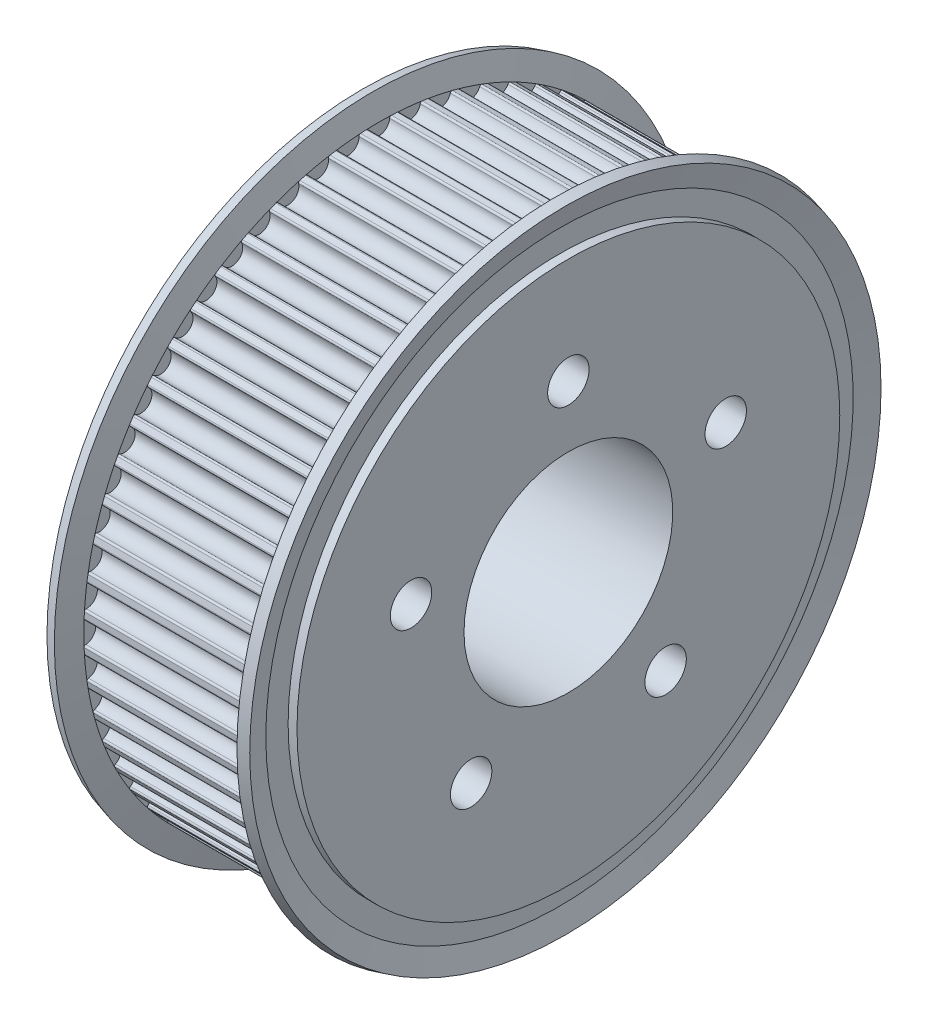
SolidWorks part; units mm, degrees
ref_plane "Front Plane" through (0, 0, 0) normal (0, 0, 1) x (1, 0, 0)
ref_plane "Top Plane" through (0, 0, 0) normal (0, 1, 0) x (1, 0, 0)
ref_plane "Right Plane" through (0, 0, 0) normal (1, 0, 0) x (0, 0, -1)
ref_plane "Plane1" through (0, 0, 0) normal (0, 0, 1) x (1, 0, 0)
sketch "Sketch1" plane through (0, 0, 0) normal (0, 0, 1) x (1, 0, 0)
  line L0 (0, 0) -> (0, 26)
  line L1 (0, 26) -> (0.85, 26)
  line L2 (0.85, 26) -> (0.85, 28.1383)
  line L3 (0.85, 28.1383) -> (0.2865, 30.2412)
  line L4 (0.2865, 30.2412) -> (1.2525, 30.5)
  line L5 (1.2525, 30.5) -> (1.85, 28.27)
  line L6 (1.85, 28.27) -> (18.15, 28.27)
  line L7 (18.15, 28.27) -> (18.7475, 30.5)
  line L8 (18.7475, 30.5) -> (19.7135, 30.2412)
  line L9 (19.7135, 30.2412) -> (19.15, 28.1383)
  line L10 (19.15, 28.1383) -> (19.15, 26)
  line L11 (19.15, 26) -> (20, 26)
  line L12 (20, 26) -> (20, 0)
  line L13 (20, 0) -> (0, 0)
  line L14 (20, 0) -> (0, 0) construction
revolve "Revolve1" add sketch "Sketch1" angle 360 about L14 reverse direction yes
ref_plane "Plane2" through (10, 0, 0) normal (1, 0, 0) x (0, 0, -1)
sketch "Sketch2" plane through (10, 0, 0) normal (1, 0, 0) x (0, 0, -1)
  line L0 (-1.2204, 28.624) -> (-1.2042, 28.2443)
  line L1 (1.2042, 28.2443) -> (1.2204, 28.624)
  arc A0 (-1.2042, 28.2443) -> (-1.0274, 28.0866) centre (-1.1969, 28.0745) cw
  arc A1 (-1.0274, 28.0866) -> (1.0274, 28.0866) centre (0, 28.16) ccw
  arc A2 (1.0274, 28.0866) -> (1.2042, 28.2443) centre (1.1969, 28.0745) cw
  arc A3 (1.2204, 28.624) -> (-1.2204, 28.624) centre (0, 0) ccw
extrude "Cut-Extrude1" cut sketch "Sketch2" against normal blind 8.15 and the other way blind 8.15
ref_plane "Plane3" through (10, 0, 0) normal (1, 0, 0) x (0, 0, -1)
sketch "Sketch3" plane through (10, 0, 0) normal (1, 0, 0) x (0, 0, -1)
  line L0 (-4.2057, 28.3396) -> (-4.1499, 27.9637)
  line L1 (-1.7547, 28.2155) -> (-1.7783, 28.5948)
  arc A0 (-4.1499, 27.9637) -> (-3.9576, 27.8254) centre (-4.125, 27.7956) cw
  arc A1 (-3.9576, 27.8254) -> (-1.9141, 28.0401) centre (-2.9435, 28.0057) ccw
  arc A2 (-1.9141, 28.0401) -> (-1.7547, 28.2155) centre (-1.7442, 28.0458) cw
  arc A3 (-1.7783, 28.5948) -> (-4.2057, 28.3396) centre (0, 0) ccw
extrude "Cut-Extrude2" cut sketch "Sketch3" against normal blind 8.15 and the other way blind 8.15
ref_plane "Plane4" through (10, 0, 0) normal (1, 0, 0) x (0, 0, -1)
sketch "Sketch4" plane through (10, 0, 0) normal (1, 0, 0) x (0, 0, -1)
  line L0 (-7.145, 27.7448) -> (-7.0502, 27.3768)
  line L1 (-4.6945, 27.8775) -> (-4.7576, 28.2522)
  arc A0 (-7.0502, 27.3768) -> (-6.8445, 27.2592) centre (-7.0078, 27.2121) cw
  arc A1 (-6.8445, 27.2592) -> (-4.8346, 27.6865) centre (-5.8548, 27.5446) ccw
  arc A2 (-4.8346, 27.6865) -> (-4.6945, 27.8775) centre (-4.6662, 27.7099) cw
  arc A3 (-4.7576, 28.2522) -> (-7.145, 27.7448) centre (0, 0) ccw
extrude "Cut-Extrude3" cut sketch "Sketch4" against normal blind 8.15 and the other way blind 8.15
ref_plane "Plane5" through (10, 0, 0) normal (1, 0, 0) x (0, 0, -1)
sketch "Sketch5" plane through (10, 0, 0) normal (1, 0, 0) x (0, 0, -1)
  line L0 (-10.0059, 26.8459) -> (-9.8732, 26.4898)
  line L1 (-7.5827, 27.2341) -> (-7.6847, 27.6002)
  arc A0 (-9.8732, 26.4898) -> (-9.6563, 26.3945) centre (-9.8139, 26.3306) cw
  arc A1 (-9.6563, 26.3945) -> (-7.7021, 27.0294) centre (-8.7019, 26.7818) ccw
  arc A2 (-7.7021, 27.0294) -> (-7.5827, 27.2341) centre (-7.5371, 27.0703) cw
  arc A3 (-7.6847, 27.6002) -> (-10.0059, 26.8459) centre (0, 0) ccw
extrude "Cut-Extrude4" cut sketch "Sketch5" against normal blind 8.15 and the other way blind 8.15
ref_plane "Plane6" through (10, 0, 0) normal (1, 0, 0) x (0, 0, -1)
sketch "Sketch6" plane through (10, 0, 0) normal (1, 0, 0) x (0, 0, -1)
  line L0 (-12.7573, 25.6529) -> (-12.5881, 25.3127)
  line L1 (-10.3879, 26.2923) -> (-10.5276, 26.6457)
  arc A0 (-12.5881, 25.3127) -> (-12.3624, 25.2405) centre (-12.5124, 25.1605) cw
  arc A1 (-12.3624, 25.2405) -> (-10.4853, 26.0763) centre (-11.4537, 25.7254) ccw
  arc A2 (-10.4853, 26.0763) -> (-10.3879, 26.2923) centre (-10.3255, 26.1342) cw
  arc A3 (-10.5276, 26.6457) -> (-12.7573, 25.6529) centre (0, 0) ccw
extrude "Cut-Extrude5" cut sketch "Sketch6" against normal blind 8.15 and the other way blind 8.15
ref_plane "Plane7" through (10, 0, 0) normal (1, 0, 0) x (0, 0, -1)
sketch "Sketch7" plane through (10, 0, 0) normal (1, 0, 0) x (0, 0, -1)
  line L0 (-15.3689, 24.1789) -> (-15.165, 23.8582)
  line L1 (-13.0793, 25.0624) -> (-13.2551, 25.3993)
  arc A0 (-15.165, 23.8582) -> (-14.933, 23.81) centre (-15.0738, 23.7148) cw
  arc A1 (-14.933, 23.81) -> (-13.1536, 24.8374) centre (-14.08, 24.3873) ccw
  arc A2 (-13.1536, 24.8374) -> (-13.0793, 25.0624) centre (-13.0007, 24.9117) cw
  arc A3 (-13.2551, 25.3993) -> (-15.3689, 24.1789) centre (0, 0) ccw
extrude "Cut-Extrude6" cut sketch "Sketch7" against normal blind 8.15 and the other way blind 8.15
ref_plane "Plane8" through (10, 0, 0) normal (1, 0, 0) x (0, 0, -1)
sketch "Sketch8" plane through (10, 0, 0) normal (1, 0, 0) x (0, 0, -1)
  line L0 (-17.8121, 22.44) -> (-17.5758, 22.1423)
  line L1 (-15.6274, 23.558) -> (-15.8375, 23.8746)
  arc A0 (-17.5758, 22.1423) -> (-17.3401, 22.1187) centre (-17.4701, 22.0092) cw
  arc A1 (-17.3401, 22.1187) -> (-15.6777, 23.3264) centre (-16.552, 22.7819) ccw
  arc A2 (-15.6777, 23.3264) -> (-15.6274, 23.558) centre (-15.5334, 23.4163) cw
  arc A3 (-15.8375, 23.8746) -> (-17.8121, 22.44) centre (0, 0) ccw
extrude "Cut-Extrude7" cut sketch "Sketch8" against normal blind 8.15 and the other way blind 8.15
ref_plane "Plane9" through (10, 0, 0) normal (1, 0, 0) x (0, 0, -1)
sketch "Sketch9" plane through (10, 0, 0) normal (1, 0, 0) x (0, 0, -1)
  line L0 (-20.0601, 20.4552) -> (-19.794, 20.1839)
  line L1 (-18.0043, 21.7954) -> (-18.2463, 22.0884)
  arc A0 (-19.794, 20.1839) -> (-19.5571, 20.185) centre (-19.675, 20.0625) cw
  arc A1 (-19.5571, 20.185) -> (-18.0301, 21.5599) centre (-18.8427, 20.927) ccw
  arc A2 (-18.0301, 21.5599) -> (-18.0043, 21.7954) centre (-17.896, 21.6643) cw
  arc A3 (-18.2463, 22.0884) -> (-20.0601, 20.4552) centre (0, 0) ccw
extrude "Cut-Extrude8" cut sketch "Sketch9" against normal blind 8.15 and the other way blind 8.15
ref_plane "Plane10" through (10, 0, 0) normal (1, 0, 0) x (0, 0, -1)
sketch "Sketch10" plane through (10, 0, 0) normal (1, 0, 0) x (0, 0, -1)
  line L0 (-22.0884, 18.2463) -> (-21.7954, 18.0043)
  line L1 (-20.1839, 19.794) -> (-20.4552, 20.0601)
  arc A0 (-21.7954, 18.0043) -> (-21.5599, 18.0301) centre (-21.6643, 17.896) cw
  arc A1 (-21.5599, 18.0301) -> (-20.185, 19.5571) centre (-20.927, 18.8427) ccw
  arc A2 (-20.185, 19.5571) -> (-20.1839, 19.794) centre (-20.0625, 19.675) cw
  arc A3 (-20.4552, 20.0601) -> (-22.0884, 18.2463) centre (0, 0) ccw
extrude "Cut-Extrude9" cut sketch "Sketch10" against normal blind 8.15 and the other way blind 8.15
ref_plane "Plane11" through (10, 0, 0) normal (1, 0, 0) x (0, 0, -1)
sketch "Sketch11" plane through (10, 0, 0) normal (1, 0, 0) x (0, 0, -1)
  line L0 (-23.8746, 15.8375) -> (-23.558, 15.6274)
  line L1 (-22.1423, 17.5758) -> (-22.44, 17.8121)
  arc A0 (-23.558, 15.6274) -> (-23.3264, 15.6777) centre (-23.4163, 15.5334) cw
  arc A1 (-23.3264, 15.6777) -> (-22.1187, 17.3401) centre (-22.7819, 16.552) ccw
  arc A2 (-22.1187, 17.3401) -> (-22.1423, 17.5758) centre (-22.0092, 17.4701) cw
  arc A3 (-22.44, 17.8121) -> (-23.8746, 15.8375) centre (0, 0) ccw
extrude "Cut-Extrude10" cut sketch "Sketch11" against normal blind 8.15 and the other way blind 8.15
ref_plane "Plane12" through (10, 0, 0) normal (1, 0, 0) x (0, 0, -1)
sketch "Sketch12" plane through (10, 0, 0) normal (1, 0, 0) x (0, 0, -1)
  line L0 (-25.3993, 13.2551) -> (-25.0624, 13.0793)
  line L1 (-23.8582, 15.165) -> (-24.1789, 15.3689)
  arc A0 (-25.0624, 13.0793) -> (-24.8374, 13.1536) centre (-24.9117, 13.0007) cw
  arc A1 (-24.8374, 13.1536) -> (-23.81, 14.933) centre (-24.3873, 14.08) ccw
  arc A2 (-23.81, 14.933) -> (-23.8582, 15.165) centre (-23.7148, 15.0738) cw
  arc A3 (-24.1789, 15.3689) -> (-25.3993, 13.2551) centre (0, 0) ccw
extrude "Cut-Extrude11" cut sketch "Sketch12" against normal blind 8.15 and the other way blind 8.15
ref_plane "Plane13" through (10, 0, 0) normal (1, 0, 0) x (0, 0, -1)
sketch "Sketch13" plane through (10, 0, 0) normal (1, 0, 0) x (0, 0, -1)
  line L0 (-26.6457, 10.5276) -> (-26.2923, 10.3879)
  line L1 (-25.3127, 12.5881) -> (-25.6529, 12.7573)
  arc A0 (-26.2923, 10.3879) -> (-26.0763, 10.4853) centre (-26.1342, 10.3255) cw
  arc A1 (-26.0763, 10.4853) -> (-25.2405, 12.3624) centre (-25.7254, 11.4537) ccw
  arc A2 (-25.2405, 12.3624) -> (-25.3127, 12.5881) centre (-25.1605, 12.5124) cw
  arc A3 (-25.6529, 12.7573) -> (-26.6457, 10.5276) centre (0, 0) ccw
extrude "Cut-Extrude12" cut sketch "Sketch13" against normal blind 8.15 and the other way blind 8.15
ref_plane "Plane14" through (10, 0, 0) normal (1, 0, 0) x (0, 0, -1)
sketch "Sketch14" plane through (10, 0, 0) normal (1, 0, 0) x (0, 0, -1)
  line L0 (-27.6002, 7.6847) -> (-27.2341, 7.5827)
  line L1 (-26.4898, 9.8732) -> (-26.8459, 10.0059)
  arc A0 (-27.2341, 7.5827) -> (-27.0294, 7.7021) centre (-27.0703, 7.5371) cw
  arc A1 (-27.0294, 7.7021) -> (-26.3945, 9.6563) centre (-26.7818, 8.7019) ccw
  arc A2 (-26.3945, 9.6563) -> (-26.4898, 9.8732) centre (-26.3306, 9.8139) cw
  arc A3 (-26.8459, 10.0059) -> (-27.6002, 7.6847) centre (0, 0) ccw
extrude "Cut-Extrude13" cut sketch "Sketch14" against normal blind 8.15 and the other way blind 8.15
ref_plane "Plane15" through (10, 0, 0) normal (1, 0, 0) x (0, 0, -1)
sketch "Sketch15" plane through (10, 0, 0) normal (1, 0, 0) x (0, 0, -1)
  line L0 (-28.2522, 4.7576) -> (-27.8775, 4.6945)
  line L1 (-27.3768, 7.0502) -> (-27.7448, 7.145)
  arc A0 (-27.8775, 4.6945) -> (-27.6865, 4.8346) centre (-27.7099, 4.6662) cw
  arc A1 (-27.6865, 4.8346) -> (-27.2592, 6.8445) centre (-27.5446, 5.8548) ccw
  arc A2 (-27.2592, 6.8445) -> (-27.3768, 7.0502) centre (-27.2121, 7.0078) cw
  arc A3 (-27.7448, 7.145) -> (-28.2522, 4.7576) centre (0, 0) ccw
extrude "Cut-Extrude14" cut sketch "Sketch15" against normal blind 8.15 and the other way blind 8.15
ref_plane "Plane16" through (10, 0, 0) normal (1, 0, 0) x (0, 0, -1)
sketch "Sketch16" plane through (10, 0, 0) normal (1, 0, 0) x (0, 0, -1)
  line L0 (-28.5948, 1.7783) -> (-28.2155, 1.7547)
  line L1 (-27.9637, 4.1499) -> (-28.3396, 4.2057)
  arc A0 (-28.2155, 1.7547) -> (-28.0401, 1.9141) centre (-28.0458, 1.7442) cw
  arc A1 (-28.0401, 1.9141) -> (-27.8254, 3.9576) centre (-28.0057, 2.9435) ccw
  arc A2 (-27.8254, 3.9576) -> (-27.9637, 4.1499) centre (-27.7956, 4.125) cw
  arc A3 (-28.3396, 4.2057) -> (-28.5948, 1.7783) centre (0, 0) ccw
extrude "Cut-Extrude15" cut sketch "Sketch16" against normal blind 8.15 and the other way blind 8.15
ref_plane "Plane17" through (10, 0, 0) normal (1, 0, 0) x (0, 0, -1)
sketch "Sketch17" plane through (10, 0, 0) normal (1, 0, 0) x (0, 0, -1)
  line L0 (-28.624, -1.2204) -> (-28.2443, -1.2042)
  line L1 (-28.2443, 1.2042) -> (-28.624, 1.2204)
  arc A0 (-28.2443, -1.2042) -> (-28.0866, -1.0274) centre (-28.0745, -1.1969) cw
  arc A1 (-28.0866, -1.0274) -> (-28.0866, 1.0274) centre (-28.16, 0) ccw
  arc A2 (-28.0866, 1.0274) -> (-28.2443, 1.2042) centre (-28.0745, 1.1969) cw
  arc A3 (-28.624, 1.2204) -> (-28.624, -1.2204) centre (0, 0) ccw
extrude "Cut-Extrude16" cut sketch "Sketch17" against normal blind 8.15 and the other way blind 8.15
ref_plane "Plane18" through (10, 0, 0) normal (1, 0, 0) x (0, 0, -1)
sketch "Sketch18" plane through (10, 0, 0) normal (1, 0, 0) x (0, 0, -1)
  line L0 (-28.3396, -4.2057) -> (-27.9637, -4.1499)
  line L1 (-28.2155, -1.7547) -> (-28.5948, -1.7783)
  arc A0 (-27.9637, -4.1499) -> (-27.8254, -3.9576) centre (-27.7956, -4.125) cw
  arc A1 (-27.8254, -3.9576) -> (-28.0401, -1.9141) centre (-28.0057, -2.9435) ccw
  arc A2 (-28.0401, -1.9141) -> (-28.2155, -1.7547) centre (-28.0458, -1.7442) cw
  arc A3 (-28.5948, -1.7783) -> (-28.3396, -4.2057) centre (0, 0) ccw
extrude "Cut-Extrude17" cut sketch "Sketch18" against normal blind 8.15 and the other way blind 8.15
ref_plane "Plane19" through (10, 0, 0) normal (1, 0, 0) x (0, 0, -1)
sketch "Sketch19" plane through (10, 0, 0) normal (1, 0, 0) x (0, 0, -1)
  line L0 (-27.7448, -7.145) -> (-27.3768, -7.0502)
  line L1 (-27.8775, -4.6945) -> (-28.2522, -4.7576)
  arc A0 (-27.3768, -7.0502) -> (-27.2592, -6.8445) centre (-27.2121, -7.0078) cw
  arc A1 (-27.2592, -6.8445) -> (-27.6865, -4.8346) centre (-27.5446, -5.8548) ccw
  arc A2 (-27.6865, -4.8346) -> (-27.8775, -4.6945) centre (-27.7099, -4.6662) cw
  arc A3 (-28.2522, -4.7576) -> (-27.7448, -7.145) centre (0, 0) ccw
extrude "Cut-Extrude18" cut sketch "Sketch19" against normal blind 8.15 and the other way blind 8.15
ref_plane "Plane20" through (10, 0, 0) normal (1, 0, 0) x (0, 0, -1)
sketch "Sketch20" plane through (10, 0, 0) normal (1, 0, 0) x (0, 0, -1)
  line L0 (-26.8459, -10.0059) -> (-26.4898, -9.8732)
  line L1 (-27.2341, -7.5827) -> (-27.6002, -7.6847)
  arc A0 (-26.4898, -9.8732) -> (-26.3945, -9.6563) centre (-26.3306, -9.8139) cw
  arc A1 (-26.3945, -9.6563) -> (-27.0294, -7.7021) centre (-26.7818, -8.7019) ccw
  arc A2 (-27.0294, -7.7021) -> (-27.2341, -7.5827) centre (-27.0703, -7.5371) cw
  arc A3 (-27.6002, -7.6847) -> (-26.8459, -10.0059) centre (0, 0) ccw
extrude "Cut-Extrude19" cut sketch "Sketch20" against normal blind 8.15 and the other way blind 8.15
ref_plane "Plane21" through (10, 0, 0) normal (1, 0, 0) x (0, 0, -1)
sketch "Sketch21" plane through (10, 0, 0) normal (1, 0, 0) x (0, 0, -1)
  line L0 (-25.6529, -12.7573) -> (-25.3127, -12.5881)
  line L1 (-26.2923, -10.3879) -> (-26.6457, -10.5276)
  arc A0 (-25.3127, -12.5881) -> (-25.2405, -12.3624) centre (-25.1605, -12.5124) cw
  arc A1 (-25.2405, -12.3624) -> (-26.0763, -10.4853) centre (-25.7254, -11.4537) ccw
  arc A2 (-26.0763, -10.4853) -> (-26.2923, -10.3879) centre (-26.1342, -10.3255) cw
  arc A3 (-26.6457, -10.5276) -> (-25.6529, -12.7573) centre (0, 0) ccw
extrude "Cut-Extrude20" cut sketch "Sketch21" against normal blind 8.15 and the other way blind 8.15
ref_plane "Plane22" through (10, 0, 0) normal (1, 0, 0) x (0, 0, -1)
sketch "Sketch22" plane through (10, 0, 0) normal (1, 0, 0) x (0, 0, -1)
  line L0 (-24.1789, -15.3689) -> (-23.8582, -15.165)
  line L1 (-25.0624, -13.0793) -> (-25.3993, -13.2551)
  arc A0 (-23.8582, -15.165) -> (-23.81, -14.933) centre (-23.7148, -15.0738) cw
  arc A1 (-23.81, -14.933) -> (-24.8374, -13.1536) centre (-24.3873, -14.08) ccw
  arc A2 (-24.8374, -13.1536) -> (-25.0624, -13.0793) centre (-24.9117, -13.0007) cw
  arc A3 (-25.3993, -13.2551) -> (-24.1789, -15.3689) centre (0, 0) ccw
extrude "Cut-Extrude21" cut sketch "Sketch22" against normal blind 8.15 and the other way blind 8.15
ref_plane "Plane23" through (10, 0, 0) normal (1, 0, 0) x (0, 0, -1)
sketch "Sketch23" plane through (10, 0, 0) normal (1, 0, 0) x (0, 0, -1)
  line L0 (-22.44, -17.8121) -> (-22.1423, -17.5758)
  line L1 (-23.558, -15.6274) -> (-23.8746, -15.8375)
  arc A0 (-22.1423, -17.5758) -> (-22.1187, -17.3401) centre (-22.0092, -17.4701) cw
  arc A1 (-22.1187, -17.3401) -> (-23.3264, -15.6777) centre (-22.7819, -16.552) ccw
  arc A2 (-23.3264, -15.6777) -> (-23.558, -15.6274) centre (-23.4163, -15.5334) cw
  arc A3 (-23.8746, -15.8375) -> (-22.44, -17.8121) centre (0, 0) ccw
extrude "Cut-Extrude22" cut sketch "Sketch23" against normal blind 8.15 and the other way blind 8.15
ref_plane "Plane24" through (10, 0, 0) normal (1, 0, 0) x (0, 0, -1)
sketch "Sketch24" plane through (10, 0, 0) normal (1, 0, 0) x (0, 0, -1)
  line L0 (-20.4552, -20.0601) -> (-20.1839, -19.794)
  line L1 (-21.7954, -18.0043) -> (-22.0884, -18.2463)
  arc A0 (-20.1839, -19.794) -> (-20.185, -19.5571) centre (-20.0625, -19.675) cw
  arc A1 (-20.185, -19.5571) -> (-21.5599, -18.0301) centre (-20.927, -18.8427) ccw
  arc A2 (-21.5599, -18.0301) -> (-21.7954, -18.0043) centre (-21.6643, -17.896) cw
  arc A3 (-22.0884, -18.2463) -> (-20.4552, -20.0601) centre (0, 0) ccw
extrude "Cut-Extrude23" cut sketch "Sketch24" against normal blind 8.15 and the other way blind 8.15
ref_plane "Plane25" through (10, 0, 0) normal (1, 0, 0) x (0, 0, -1)
sketch "Sketch25" plane through (10, 0, 0) normal (1, 0, 0) x (0, 0, -1)
  line L0 (-18.2463, -22.0884) -> (-18.0043, -21.7954)
  line L1 (-19.794, -20.1839) -> (-20.0601, -20.4552)
  arc A0 (-18.0043, -21.7954) -> (-18.0301, -21.5599) centre (-17.896, -21.6643) cw
  arc A1 (-18.0301, -21.5599) -> (-19.5571, -20.185) centre (-18.8427, -20.927) ccw
  arc A2 (-19.5571, -20.185) -> (-19.794, -20.1839) centre (-19.675, -20.0625) cw
  arc A3 (-20.0601, -20.4552) -> (-18.2463, -22.0884) centre (0, 0) ccw
extrude "Cut-Extrude24" cut sketch "Sketch25" against normal blind 8.15 and the other way blind 8.15
ref_plane "Plane26" through (10, 0, 0) normal (1, 0, 0) x (0, 0, -1)
sketch "Sketch26" plane through (10, 0, 0) normal (1, 0, 0) x (0, 0, -1)
  line L0 (-15.8375, -23.8746) -> (-15.6274, -23.558)
  line L1 (-17.5758, -22.1423) -> (-17.8121, -22.44)
  arc A0 (-15.6274, -23.558) -> (-15.6777, -23.3264) centre (-15.5334, -23.4163) cw
  arc A1 (-15.6777, -23.3264) -> (-17.3401, -22.1187) centre (-16.552, -22.7819) ccw
  arc A2 (-17.3401, -22.1187) -> (-17.5758, -22.1423) centre (-17.4701, -22.0092) cw
  arc A3 (-17.8121, -22.44) -> (-15.8375, -23.8746) centre (0, 0) ccw
extrude "Cut-Extrude25" cut sketch "Sketch26" against normal blind 8.15 and the other way blind 8.15
ref_plane "Plane27" through (10, 0, 0) normal (1, 0, 0) x (0, 0, -1)
sketch "Sketch27" plane through (10, 0, 0) normal (1, 0, 0) x (0, 0, -1)
  line L0 (-13.2551, -25.3993) -> (-13.0793, -25.0624)
  line L1 (-15.165, -23.8582) -> (-15.3689, -24.1789)
  arc A0 (-13.0793, -25.0624) -> (-13.1536, -24.8374) centre (-13.0007, -24.9117) cw
  arc A1 (-13.1536, -24.8374) -> (-14.933, -23.81) centre (-14.08, -24.3873) ccw
  arc A2 (-14.933, -23.81) -> (-15.165, -23.8582) centre (-15.0738, -23.7148) cw
  arc A3 (-15.3689, -24.1789) -> (-13.2551, -25.3993) centre (0, 0) ccw
extrude "Cut-Extrude26" cut sketch "Sketch27" against normal blind 8.15 and the other way blind 8.15
ref_plane "Plane28" through (10, 0, 0) normal (1, 0, 0) x (0, 0, -1)
sketch "Sketch28" plane through (10, 0, 0) normal (1, 0, 0) x (0, 0, -1)
  line L0 (-10.5276, -26.6457) -> (-10.3879, -26.2923)
  line L1 (-12.5881, -25.3127) -> (-12.7573, -25.6529)
  arc A0 (-10.3879, -26.2923) -> (-10.4853, -26.0763) centre (-10.3255, -26.1342) cw
  arc A1 (-10.4853, -26.0763) -> (-12.3624, -25.2405) centre (-11.4537, -25.7254) ccw
  arc A2 (-12.3624, -25.2405) -> (-12.5881, -25.3127) centre (-12.5124, -25.1605) cw
  arc A3 (-12.7573, -25.6529) -> (-10.5276, -26.6457) centre (0, 0) ccw
extrude "Cut-Extrude27" cut sketch "Sketch28" against normal blind 8.15 and the other way blind 8.15
ref_plane "Plane29" through (10, 0, 0) normal (1, 0, 0) x (0, 0, -1)
sketch "Sketch29" plane through (10, 0, 0) normal (1, 0, 0) x (0, 0, -1)
  line L0 (-7.6847, -27.6002) -> (-7.5827, -27.2341)
  line L1 (-9.8732, -26.4898) -> (-10.0059, -26.8459)
  arc A0 (-7.5827, -27.2341) -> (-7.7021, -27.0294) centre (-7.5371, -27.0703) cw
  arc A1 (-7.7021, -27.0294) -> (-9.6563, -26.3945) centre (-8.7019, -26.7818) ccw
  arc A2 (-9.6563, -26.3945) -> (-9.8732, -26.4898) centre (-9.8139, -26.3306) cw
  arc A3 (-10.0059, -26.8459) -> (-7.6847, -27.6002) centre (0, 0) ccw
extrude "Cut-Extrude28" cut sketch "Sketch29" against normal blind 8.15 and the other way blind 8.15
ref_plane "Plane30" through (10, 0, 0) normal (1, 0, 0) x (0, 0, -1)
sketch "Sketch30" plane through (10, 0, 0) normal (1, 0, 0) x (0, 0, -1)
  line L0 (-4.7576, -28.2522) -> (-4.6945, -27.8775)
  line L1 (-7.0502, -27.3768) -> (-7.145, -27.7448)
  arc A0 (-4.6945, -27.8775) -> (-4.8346, -27.6865) centre (-4.6662, -27.7099) cw
  arc A1 (-4.8346, -27.6865) -> (-6.8445, -27.2592) centre (-5.8548, -27.5446) ccw
  arc A2 (-6.8445, -27.2592) -> (-7.0502, -27.3768) centre (-7.0078, -27.2121) cw
  arc A3 (-7.145, -27.7448) -> (-4.7576, -28.2522) centre (0, 0) ccw
extrude "Cut-Extrude29" cut sketch "Sketch30" against normal blind 8.15 and the other way blind 8.15
ref_plane "Plane31" through (10, 0, 0) normal (1, 0, 0) x (0, 0, -1)
sketch "Sketch31" plane through (10, 0, 0) normal (1, 0, 0) x (0, 0, -1)
  line L0 (-1.7783, -28.5948) -> (-1.7547, -28.2155)
  line L1 (-4.1499, -27.9637) -> (-4.2057, -28.3396)
  arc A0 (-1.7547, -28.2155) -> (-1.9141, -28.0401) centre (-1.7442, -28.0458) cw
  arc A1 (-1.9141, -28.0401) -> (-3.9576, -27.8254) centre (-2.9435, -28.0057) ccw
  arc A2 (-3.9576, -27.8254) -> (-4.1499, -27.9637) centre (-4.125, -27.7956) cw
  arc A3 (-4.2057, -28.3396) -> (-1.7783, -28.5948) centre (0, 0) ccw
extrude "Cut-Extrude30" cut sketch "Sketch31" against normal blind 8.15 and the other way blind 8.15
ref_plane "Plane32" through (10, 0, 0) normal (1, 0, 0) x (0, 0, -1)
sketch "Sketch32" plane through (10, 0, 0) normal (1, 0, 0) x (0, 0, -1)
  line L0 (1.2204, -28.624) -> (1.2042, -28.2443)
  line L1 (-1.2042, -28.2443) -> (-1.2204, -28.624)
  arc A0 (1.2042, -28.2443) -> (1.0274, -28.0866) centre (1.1969, -28.0745) cw
  arc A1 (1.0274, -28.0866) -> (-1.0274, -28.0866) centre (0, -28.16) ccw
  arc A2 (-1.0274, -28.0866) -> (-1.2042, -28.2443) centre (-1.1969, -28.0745) cw
  arc A3 (-1.2204, -28.624) -> (1.2204, -28.624) centre (0, 0) ccw
extrude "Cut-Extrude31" cut sketch "Sketch32" against normal blind 8.15 and the other way blind 8.15
ref_plane "Plane33" through (10, 0, 0) normal (1, 0, 0) x (0, 0, -1)
sketch "Sketch33" plane through (10, 0, 0) normal (1, 0, 0) x (0, 0, -1)
  line L0 (4.2057, -28.3396) -> (4.1499, -27.9637)
  line L1 (1.7547, -28.2155) -> (1.7783, -28.5948)
  arc A0 (4.1499, -27.9637) -> (3.9576, -27.8254) centre (4.125, -27.7956) cw
  arc A1 (3.9576, -27.8254) -> (1.9141, -28.0401) centre (2.9435, -28.0057) ccw
  arc A2 (1.9141, -28.0401) -> (1.7547, -28.2155) centre (1.7442, -28.0458) cw
  arc A3 (1.7783, -28.5948) -> (4.2057, -28.3396) centre (0, 0) ccw
extrude "Cut-Extrude32" cut sketch "Sketch33" against normal blind 8.15 and the other way blind 8.15
ref_plane "Plane34" through (10, 0, 0) normal (1, 0, 0) x (0, 0, -1)
sketch "Sketch34" plane through (10, 0, 0) normal (1, 0, 0) x (0, 0, -1)
  line L0 (7.145, -27.7448) -> (7.0502, -27.3768)
  line L1 (4.6945, -27.8775) -> (4.7576, -28.2522)
  arc A0 (7.0502, -27.3768) -> (6.8445, -27.2592) centre (7.0078, -27.2121) cw
  arc A1 (6.8445, -27.2592) -> (4.8346, -27.6865) centre (5.8548, -27.5446) ccw
  arc A2 (4.8346, -27.6865) -> (4.6945, -27.8775) centre (4.6662, -27.7099) cw
  arc A3 (4.7576, -28.2522) -> (7.145, -27.7448) centre (0, 0) ccw
extrude "Cut-Extrude33" cut sketch "Sketch34" against normal blind 8.15 and the other way blind 8.15
ref_plane "Plane35" through (10, 0, 0) normal (1, 0, 0) x (0, 0, -1)
sketch "Sketch35" plane through (10, 0, 0) normal (1, 0, 0) x (0, 0, -1)
  line L0 (10.0059, -26.8459) -> (9.8732, -26.4898)
  line L1 (7.5827, -27.2341) -> (7.6847, -27.6002)
  arc A0 (9.8732, -26.4898) -> (9.6563, -26.3945) centre (9.8139, -26.3306) cw
  arc A1 (9.6563, -26.3945) -> (7.7021, -27.0294) centre (8.7019, -26.7818) ccw
  arc A2 (7.7021, -27.0294) -> (7.5827, -27.2341) centre (7.5371, -27.0703) cw
  arc A3 (7.6847, -27.6002) -> (10.0059, -26.8459) centre (0, 0) ccw
extrude "Cut-Extrude34" cut sketch "Sketch35" against normal blind 8.15 and the other way blind 8.15
ref_plane "Plane36" through (10, 0, 0) normal (1, 0, 0) x (0, 0, -1)
sketch "Sketch36" plane through (10, 0, 0) normal (1, 0, 0) x (0, 0, -1)
  line L0 (12.7573, -25.6529) -> (12.5881, -25.3127)
  line L1 (10.3879, -26.2923) -> (10.5276, -26.6457)
  arc A0 (12.5881, -25.3127) -> (12.3624, -25.2405) centre (12.5124, -25.1605) cw
  arc A1 (12.3624, -25.2405) -> (10.4853, -26.0763) centre (11.4537, -25.7254) ccw
  arc A2 (10.4853, -26.0763) -> (10.3879, -26.2923) centre (10.3255, -26.1342) cw
  arc A3 (10.5276, -26.6457) -> (12.7573, -25.6529) centre (0, 0) ccw
extrude "Cut-Extrude35" cut sketch "Sketch36" against normal blind 8.15 and the other way blind 8.15
ref_plane "Plane37" through (10, 0, 0) normal (1, 0, 0) x (0, 0, -1)
sketch "Sketch37" plane through (10, 0, 0) normal (1, 0, 0) x (0, 0, -1)
  line L0 (15.3689, -24.1789) -> (15.165, -23.8582)
  line L1 (13.0793, -25.0624) -> (13.2551, -25.3993)
  arc A0 (15.165, -23.8582) -> (14.933, -23.81) centre (15.0738, -23.7148) cw
  arc A1 (14.933, -23.81) -> (13.1536, -24.8374) centre (14.08, -24.3873) ccw
  arc A2 (13.1536, -24.8374) -> (13.0793, -25.0624) centre (13.0007, -24.9117) cw
  arc A3 (13.2551, -25.3993) -> (15.3689, -24.1789) centre (0, 0) ccw
extrude "Cut-Extrude36" cut sketch "Sketch37" against normal blind 8.15 and the other way blind 8.15
ref_plane "Plane38" through (10, 0, 0) normal (1, 0, 0) x (0, 0, -1)
sketch "Sketch38" plane through (10, 0, 0) normal (1, 0, 0) x (0, 0, -1)
  line L0 (17.8121, -22.44) -> (17.5758, -22.1423)
  line L1 (15.6274, -23.558) -> (15.8375, -23.8746)
  arc A0 (17.5758, -22.1423) -> (17.3401, -22.1187) centre (17.4701, -22.0092) cw
  arc A1 (17.3401, -22.1187) -> (15.6777, -23.3264) centre (16.552, -22.7819) ccw
  arc A2 (15.6777, -23.3264) -> (15.6274, -23.558) centre (15.5334, -23.4163) cw
  arc A3 (15.8375, -23.8746) -> (17.8121, -22.44) centre (0, 0) ccw
extrude "Cut-Extrude37" cut sketch "Sketch38" against normal blind 8.15 and the other way blind 8.15
ref_plane "Plane39" through (10, 0, 0) normal (1, 0, 0) x (0, 0, -1)
sketch "Sketch39" plane through (10, 0, 0) normal (1, 0, 0) x (0, 0, -1)
  line L0 (20.0601, -20.4552) -> (19.794, -20.1839)
  line L1 (18.0043, -21.7954) -> (18.2463, -22.0884)
  arc A0 (19.794, -20.1839) -> (19.5571, -20.185) centre (19.675, -20.0625) cw
  arc A1 (19.5571, -20.185) -> (18.0301, -21.5599) centre (18.8427, -20.927) ccw
  arc A2 (18.0301, -21.5599) -> (18.0043, -21.7954) centre (17.896, -21.6643) cw
  arc A3 (18.2463, -22.0884) -> (20.0601, -20.4552) centre (0, 0) ccw
extrude "Cut-Extrude38" cut sketch "Sketch39" against normal blind 8.15 and the other way blind 8.15
ref_plane "Plane40" through (10, 0, 0) normal (1, 0, 0) x (0, 0, -1)
sketch "Sketch40" plane through (10, 0, 0) normal (1, 0, 0) x (0, 0, -1)
  line L0 (22.0884, -18.2463) -> (21.7954, -18.0043)
  line L1 (20.1839, -19.794) -> (20.4552, -20.0601)
  arc A0 (21.7954, -18.0043) -> (21.5599, -18.0301) centre (21.6643, -17.896) cw
  arc A1 (21.5599, -18.0301) -> (20.185, -19.5571) centre (20.927, -18.8427) ccw
  arc A2 (20.185, -19.5571) -> (20.1839, -19.794) centre (20.0625, -19.675) cw
  arc A3 (20.4552, -20.0601) -> (22.0884, -18.2463) centre (0, 0) ccw
extrude "Cut-Extrude39" cut sketch "Sketch40" against normal blind 8.15 and the other way blind 8.15
ref_plane "Plane41" through (10, 0, 0) normal (1, 0, 0) x (0, 0, -1)
sketch "Sketch41" plane through (10, 0, 0) normal (1, 0, 0) x (0, 0, -1)
  line L0 (23.8746, -15.8375) -> (23.558, -15.6274)
  line L1 (22.1423, -17.5758) -> (22.44, -17.8121)
  arc A0 (23.558, -15.6274) -> (23.3264, -15.6777) centre (23.4163, -15.5334) cw
  arc A1 (23.3264, -15.6777) -> (22.1187, -17.3401) centre (22.7819, -16.552) ccw
  arc A2 (22.1187, -17.3401) -> (22.1423, -17.5758) centre (22.0092, -17.4701) cw
  arc A3 (22.44, -17.8121) -> (23.8746, -15.8375) centre (0, 0) ccw
extrude "Cut-Extrude40" cut sketch "Sketch41" against normal blind 8.15 and the other way blind 8.15
ref_plane "Plane42" through (10, 0, 0) normal (1, 0, 0) x (0, 0, -1)
sketch "Sketch42" plane through (10, 0, 0) normal (1, 0, 0) x (0, 0, -1)
  line L0 (25.3993, -13.2551) -> (25.0624, -13.0793)
  line L1 (23.8582, -15.165) -> (24.1789, -15.3689)
  arc A0 (25.0624, -13.0793) -> (24.8374, -13.1536) centre (24.9117, -13.0007) cw
  arc A1 (24.8374, -13.1536) -> (23.81, -14.933) centre (24.3873, -14.08) ccw
  arc A2 (23.81, -14.933) -> (23.8582, -15.165) centre (23.7148, -15.0738) cw
  arc A3 (24.1789, -15.3689) -> (25.3993, -13.2551) centre (0, 0) ccw
extrude "Cut-Extrude41" cut sketch "Sketch42" against normal blind 8.15 and the other way blind 8.15
ref_plane "Plane43" through (10, 0, 0) normal (1, 0, 0) x (0, 0, -1)
sketch "Sketch43" plane through (10, 0, 0) normal (1, 0, 0) x (0, 0, -1)
  line L0 (26.6457, -10.5276) -> (26.2923, -10.3879)
  line L1 (25.3127, -12.5881) -> (25.6529, -12.7573)
  arc A0 (26.2923, -10.3879) -> (26.0763, -10.4853) centre (26.1342, -10.3255) cw
  arc A1 (26.0763, -10.4853) -> (25.2405, -12.3624) centre (25.7254, -11.4537) ccw
  arc A2 (25.2405, -12.3624) -> (25.3127, -12.5881) centre (25.1605, -12.5124) cw
  arc A3 (25.6529, -12.7573) -> (26.6457, -10.5276) centre (0, 0) ccw
extrude "Cut-Extrude42" cut sketch "Sketch43" against normal blind 8.15 and the other way blind 8.15
ref_plane "Plane44" through (10, 0, 0) normal (1, 0, 0) x (0, 0, -1)
sketch "Sketch44" plane through (10, 0, 0) normal (1, 0, 0) x (0, 0, -1)
  line L0 (27.6002, -7.6847) -> (27.2341, -7.5827)
  line L1 (26.4898, -9.8732) -> (26.8459, -10.0059)
  arc A0 (27.2341, -7.5827) -> (27.0294, -7.7021) centre (27.0703, -7.5371) cw
  arc A1 (27.0294, -7.7021) -> (26.3945, -9.6563) centre (26.7818, -8.7019) ccw
  arc A2 (26.3945, -9.6563) -> (26.4898, -9.8732) centre (26.3306, -9.8139) cw
  arc A3 (26.8459, -10.0059) -> (27.6002, -7.6847) centre (0, 0) ccw
extrude "Cut-Extrude43" cut sketch "Sketch44" against normal blind 8.15 and the other way blind 8.15
ref_plane "Plane45" through (10, 0, 0) normal (1, 0, 0) x (0, 0, -1)
sketch "Sketch45" plane through (10, 0, 0) normal (1, 0, 0) x (0, 0, -1)
  line L0 (28.2522, -4.7576) -> (27.8775, -4.6945)
  line L1 (27.3768, -7.0502) -> (27.7448, -7.145)
  arc A0 (27.8775, -4.6945) -> (27.6865, -4.8346) centre (27.7099, -4.6662) cw
  arc A1 (27.6865, -4.8346) -> (27.2592, -6.8445) centre (27.5446, -5.8548) ccw
  arc A2 (27.2592, -6.8445) -> (27.3768, -7.0502) centre (27.2121, -7.0078) cw
  arc A3 (27.7448, -7.145) -> (28.2522, -4.7576) centre (0, 0) ccw
extrude "Cut-Extrude44" cut sketch "Sketch45" against normal blind 8.15 and the other way blind 8.15
ref_plane "Plane46" through (10, 0, 0) normal (1, 0, 0) x (0, 0, -1)
sketch "Sketch46" plane through (10, 0, 0) normal (1, 0, 0) x (0, 0, -1)
  line L0 (28.5948, -1.7783) -> (28.2155, -1.7547)
  line L1 (27.9637, -4.1499) -> (28.3396, -4.2057)
  arc A0 (28.2155, -1.7547) -> (28.0401, -1.9141) centre (28.0458, -1.7442) cw
  arc A1 (28.0401, -1.9141) -> (27.8254, -3.9576) centre (28.0057, -2.9435) ccw
  arc A2 (27.8254, -3.9576) -> (27.9637, -4.1499) centre (27.7956, -4.125) cw
  arc A3 (28.3396, -4.2057) -> (28.5948, -1.7783) centre (0, 0) ccw
extrude "Cut-Extrude45" cut sketch "Sketch46" against normal blind 8.15 and the other way blind 8.15
ref_plane "Plane47" through (10, 0, 0) normal (1, 0, 0) x (0, 0, -1)
sketch "Sketch47" plane through (10, 0, 0) normal (1, 0, 0) x (0, 0, -1)
  line L0 (28.624, 1.2204) -> (28.2443, 1.2042)
  line L1 (28.2443, -1.2042) -> (28.624, -1.2204)
  arc A0 (28.2443, 1.2042) -> (28.0866, 1.0274) centre (28.0745, 1.1969) cw
  arc A1 (28.0866, 1.0274) -> (28.0866, -1.0274) centre (28.16, 0) ccw
  arc A2 (28.0866, -1.0274) -> (28.2443, -1.2042) centre (28.0745, -1.1969) cw
  arc A3 (28.624, -1.2204) -> (28.624, 1.2204) centre (0, 0) ccw
extrude "Cut-Extrude46" cut sketch "Sketch47" against normal blind 8.15 and the other way blind 8.15
ref_plane "Plane48" through (10, 0, 0) normal (1, 0, 0) x (0, 0, -1)
sketch "Sketch48" plane through (10, 0, 0) normal (1, 0, 0) x (0, 0, -1)
  line L0 (28.3396, 4.2057) -> (27.9637, 4.1499)
  line L1 (28.2155, 1.7547) -> (28.5948, 1.7783)
  arc A0 (27.9637, 4.1499) -> (27.8254, 3.9576) centre (27.7956, 4.125) cw
  arc A1 (27.8254, 3.9576) -> (28.0401, 1.9141) centre (28.0057, 2.9435) ccw
  arc A2 (28.0401, 1.9141) -> (28.2155, 1.7547) centre (28.0458, 1.7442) cw
  arc A3 (28.5948, 1.7783) -> (28.3396, 4.2057) centre (0, 0) ccw
extrude "Cut-Extrude47" cut sketch "Sketch48" against normal blind 8.15 and the other way blind 8.15
ref_plane "Plane49" through (10, 0, 0) normal (1, 0, 0) x (0, 0, -1)
sketch "Sketch49" plane through (10, 0, 0) normal (1, 0, 0) x (0, 0, -1)
  line L0 (27.7448, 7.145) -> (27.3768, 7.0502)
  line L1 (27.8775, 4.6945) -> (28.2522, 4.7576)
  arc A0 (27.3768, 7.0502) -> (27.2592, 6.8445) centre (27.2121, 7.0078) cw
  arc A1 (27.2592, 6.8445) -> (27.6865, 4.8346) centre (27.5446, 5.8548) ccw
  arc A2 (27.6865, 4.8346) -> (27.8775, 4.6945) centre (27.7099, 4.6662) cw
  arc A3 (28.2522, 4.7576) -> (27.7448, 7.145) centre (0, 0) ccw
extrude "Cut-Extrude48" cut sketch "Sketch49" against normal blind 8.15 and the other way blind 8.15
ref_plane "Plane50" through (10, 0, 0) normal (1, 0, 0) x (0, 0, -1)
sketch "Sketch50" plane through (10, 0, 0) normal (1, 0, 0) x (0, 0, -1)
  line L0 (26.8459, 10.0059) -> (26.4898, 9.8732)
  line L1 (27.2341, 7.5827) -> (27.6002, 7.6847)
  arc A0 (26.4898, 9.8732) -> (26.3945, 9.6563) centre (26.3306, 9.8139) cw
  arc A1 (26.3945, 9.6563) -> (27.0294, 7.7021) centre (26.7818, 8.7019) ccw
  arc A2 (27.0294, 7.7021) -> (27.2341, 7.5827) centre (27.0703, 7.5371) cw
  arc A3 (27.6002, 7.6847) -> (26.8459, 10.0059) centre (0, 0) ccw
extrude "Cut-Extrude49" cut sketch "Sketch50" against normal blind 8.15 and the other way blind 8.15
ref_plane "Plane51" through (10, 0, 0) normal (1, 0, 0) x (0, 0, -1)
sketch "Sketch51" plane through (10, 0, 0) normal (1, 0, 0) x (0, 0, -1)
  line L0 (25.6529, 12.7573) -> (25.3127, 12.5881)
  line L1 (26.2923, 10.3879) -> (26.6457, 10.5276)
  arc A0 (25.3127, 12.5881) -> (25.2405, 12.3624) centre (25.1605, 12.5124) cw
  arc A1 (25.2405, 12.3624) -> (26.0763, 10.4853) centre (25.7254, 11.4537) ccw
  arc A2 (26.0763, 10.4853) -> (26.2923, 10.3879) centre (26.1342, 10.3255) cw
  arc A3 (26.6457, 10.5276) -> (25.6529, 12.7573) centre (0, 0) ccw
extrude "Cut-Extrude50" cut sketch "Sketch51" against normal blind 8.15 and the other way blind 8.15
ref_plane "Plane52" through (10, 0, 0) normal (1, 0, 0) x (0, 0, -1)
sketch "Sketch52" plane through (10, 0, 0) normal (1, 0, 0) x (0, 0, -1)
  line L0 (24.1789, 15.3689) -> (23.8582, 15.165)
  line L1 (25.0624, 13.0793) -> (25.3993, 13.2551)
  arc A0 (23.8582, 15.165) -> (23.81, 14.933) centre (23.7148, 15.0738) cw
  arc A1 (23.81, 14.933) -> (24.8374, 13.1536) centre (24.3873, 14.08) ccw
  arc A2 (24.8374, 13.1536) -> (25.0624, 13.0793) centre (24.9117, 13.0007) cw
  arc A3 (25.3993, 13.2551) -> (24.1789, 15.3689) centre (0, 0) ccw
extrude "Cut-Extrude51" cut sketch "Sketch52" against normal blind 8.15 and the other way blind 8.15
ref_plane "Plane53" through (10, 0, 0) normal (1, 0, 0) x (0, 0, -1)
sketch "Sketch53" plane through (10, 0, 0) normal (1, 0, 0) x (0, 0, -1)
  line L0 (22.44, 17.8121) -> (22.1423, 17.5758)
  line L1 (23.558, 15.6274) -> (23.8746, 15.8375)
  arc A0 (22.1423, 17.5758) -> (22.1187, 17.3401) centre (22.0092, 17.4701) cw
  arc A1 (22.1187, 17.3401) -> (23.3264, 15.6777) centre (22.7819, 16.552) ccw
  arc A2 (23.3264, 15.6777) -> (23.558, 15.6274) centre (23.4163, 15.5334) cw
  arc A3 (23.8746, 15.8375) -> (22.44, 17.8121) centre (0, 0) ccw
extrude "Cut-Extrude52" cut sketch "Sketch53" against normal blind 8.15 and the other way blind 8.15
ref_plane "Plane54" through (10, 0, 0) normal (1, 0, 0) x (0, 0, -1)
sketch "Sketch54" plane through (10, 0, 0) normal (1, 0, 0) x (0, 0, -1)
  line L0 (20.4552, 20.0601) -> (20.1839, 19.794)
  line L1 (21.7954, 18.0043) -> (22.0884, 18.2463)
  arc A0 (20.1839, 19.794) -> (20.185, 19.5571) centre (20.0625, 19.675) cw
  arc A1 (20.185, 19.5571) -> (21.5599, 18.0301) centre (20.927, 18.8427) ccw
  arc A2 (21.5599, 18.0301) -> (21.7954, 18.0043) centre (21.6643, 17.896) cw
  arc A3 (22.0884, 18.2463) -> (20.4552, 20.0601) centre (0, 0) ccw
extrude "Cut-Extrude53" cut sketch "Sketch54" against normal blind 8.15 and the other way blind 8.15
ref_plane "Plane55" through (10, 0, 0) normal (1, 0, 0) x (0, 0, -1)
sketch "Sketch55" plane through (10, 0, 0) normal (1, 0, 0) x (0, 0, -1)
  line L0 (18.2463, 22.0884) -> (18.0043, 21.7954)
  line L1 (19.794, 20.1839) -> (20.0601, 20.4552)
  arc A0 (18.0043, 21.7954) -> (18.0301, 21.5599) centre (17.896, 21.6643) cw
  arc A1 (18.0301, 21.5599) -> (19.5571, 20.185) centre (18.8427, 20.927) ccw
  arc A2 (19.5571, 20.185) -> (19.794, 20.1839) centre (19.675, 20.0625) cw
  arc A3 (20.0601, 20.4552) -> (18.2463, 22.0884) centre (0, 0) ccw
extrude "Cut-Extrude54" cut sketch "Sketch55" against normal blind 8.15 and the other way blind 8.15
ref_plane "Plane56" through (10, 0, 0) normal (1, 0, 0) x (0, 0, -1)
sketch "Sketch56" plane through (10, 0, 0) normal (1, 0, 0) x (0, 0, -1)
  line L0 (15.8375, 23.8746) -> (15.6274, 23.558)
  line L1 (17.5758, 22.1423) -> (17.8121, 22.44)
  arc A0 (15.6274, 23.558) -> (15.6777, 23.3264) centre (15.5334, 23.4163) cw
  arc A1 (15.6777, 23.3264) -> (17.3401, 22.1187) centre (16.552, 22.7819) ccw
  arc A2 (17.3401, 22.1187) -> (17.5758, 22.1423) centre (17.4701, 22.0092) cw
  arc A3 (17.8121, 22.44) -> (15.8375, 23.8746) centre (0, 0) ccw
extrude "Cut-Extrude55" cut sketch "Sketch56" against normal blind 8.15 and the other way blind 8.15
ref_plane "Plane57" through (10, 0, 0) normal (1, 0, 0) x (0, 0, -1)
sketch "Sketch57" plane through (10, 0, 0) normal (1, 0, 0) x (0, 0, -1)
  line L0 (13.2551, 25.3993) -> (13.0793, 25.0624)
  line L1 (15.165, 23.8582) -> (15.3689, 24.1789)
  arc A0 (13.0793, 25.0624) -> (13.1536, 24.8374) centre (13.0007, 24.9117) cw
  arc A1 (13.1536, 24.8374) -> (14.933, 23.81) centre (14.08, 24.3873) ccw
  arc A2 (14.933, 23.81) -> (15.165, 23.8582) centre (15.0738, 23.7148) cw
  arc A3 (15.3689, 24.1789) -> (13.2551, 25.3993) centre (0, 0) ccw
extrude "Cut-Extrude56" cut sketch "Sketch57" against normal blind 8.15 and the other way blind 8.15
ref_plane "Plane58" through (10, 0, 0) normal (1, 0, 0) x (0, 0, -1)
sketch "Sketch58" plane through (10, 0, 0) normal (1, 0, 0) x (0, 0, -1)
  line L0 (10.5276, 26.6457) -> (10.3879, 26.2923)
  line L1 (12.5881, 25.3127) -> (12.7573, 25.6529)
  arc A0 (10.3879, 26.2923) -> (10.4853, 26.0763) centre (10.3255, 26.1342) cw
  arc A1 (10.4853, 26.0763) -> (12.3624, 25.2405) centre (11.4537, 25.7254) ccw
  arc A2 (12.3624, 25.2405) -> (12.5881, 25.3127) centre (12.5124, 25.1605) cw
  arc A3 (12.7573, 25.6529) -> (10.5276, 26.6457) centre (0, 0) ccw
extrude "Cut-Extrude57" cut sketch "Sketch58" against normal blind 8.15 and the other way blind 8.15
ref_plane "Plane59" through (10, 0, 0) normal (1, 0, 0) x (0, 0, -1)
sketch "Sketch59" plane through (10, 0, 0) normal (1, 0, 0) x (0, 0, -1)
  line L0 (7.6847, 27.6002) -> (7.5827, 27.2341)
  line L1 (9.8732, 26.4898) -> (10.0059, 26.8459)
  arc A0 (7.5827, 27.2341) -> (7.7021, 27.0294) centre (7.5371, 27.0703) cw
  arc A1 (7.7021, 27.0294) -> (9.6563, 26.3945) centre (8.7019, 26.7818) ccw
  arc A2 (9.6563, 26.3945) -> (9.8732, 26.4898) centre (9.8139, 26.3306) cw
  arc A3 (10.0059, 26.8459) -> (7.6847, 27.6002) centre (0, 0) ccw
extrude "Cut-Extrude58" cut sketch "Sketch59" against normal blind 8.15 and the other way blind 8.15
ref_plane "Plane60" through (10, 0, 0) normal (1, 0, 0) x (0, 0, -1)
sketch "Sketch60" plane through (10, 0, 0) normal (1, 0, 0) x (0, 0, -1)
  line L0 (4.7576, 28.2522) -> (4.6945, 27.8775)
  line L1 (7.0502, 27.3768) -> (7.145, 27.7448)
  arc A0 (4.6945, 27.8775) -> (4.8346, 27.6865) centre (4.6662, 27.7099) cw
  arc A1 (4.8346, 27.6865) -> (6.8445, 27.2592) centre (5.8548, 27.5446) ccw
  arc A2 (6.8445, 27.2592) -> (7.0502, 27.3768) centre (7.0078, 27.2121) cw
  arc A3 (7.145, 27.7448) -> (4.7576, 28.2522) centre (0, 0) ccw
extrude "Cut-Extrude59" cut sketch "Sketch60" against normal blind 8.15 and the other way blind 8.15
ref_plane "Plane61" through (10, 0, 0) normal (1, 0, 0) x (0, 0, -1)
sketch "Sketch61" plane through (10, 0, 0) normal (1, 0, 0) x (0, 0, -1)
  line L0 (1.7783, 28.5948) -> (1.7547, 28.2155)
  line L1 (4.1499, 27.9637) -> (4.2057, 28.3396)
  arc A0 (1.7547, 28.2155) -> (1.9141, 28.0401) centre (1.7442, 28.0458) cw
  arc A1 (1.9141, 28.0401) -> (3.9576, 27.8254) centre (2.9435, 28.0057) ccw
  arc A2 (3.9576, 27.8254) -> (4.1499, 27.9637) centre (4.125, 27.7956) cw
  arc A3 (4.2057, 28.3396) -> (1.7783, 28.5948) centre (0, 0) ccw
extrude "Cut-Extrude60" cut sketch "Sketch61" against normal blind 8.15 and the other way blind 8.15
ref_plane "Plane62" through (0, 0, 0) normal (0, 0, 1) x (1, 0, 0)
sketch "Sketch62" plane through (0, 0, 0) normal (0, 0, 1) x (1, 0, 0)
  line L0 (0, 0) -> (0, 10)
  line L1 (0, 10) -> (20, 10)
  line L2 (20, 10) -> (20, 0)
  line L3 (20, 0) -> (0, 0)
  line L4 (20, 0) -> (0, 0) construction
revolve "Cut-Revolve1" cut sketch "Sketch62" angle 360 about L4 reverse direction yes
sketch "Sketch63" plane through (20, 0, 0) normal (1, 0, 0) x (0, 0, -1)
  circle A0 centre (0, 15.85) radius 1.9844
  circle A1 centre (15.0742, 4.8979) radius 1.9844
  circle A2 centre (9.3164, -12.8229) radius 1.9844
  circle A3 centre (-9.3164, -12.8229) radius 1.9844
  circle A4 centre (-15.0742, 4.8979) radius 1.9844
  point P2 (0, 0)
  point P14 (0, 0)
  dimension "D1" = 15.85
  dimension "D3" = 3.9688
  dimension "D2" = 5
extrude "Cut-Extrude61" cut sketch "Sketch63" against normal blind 18
